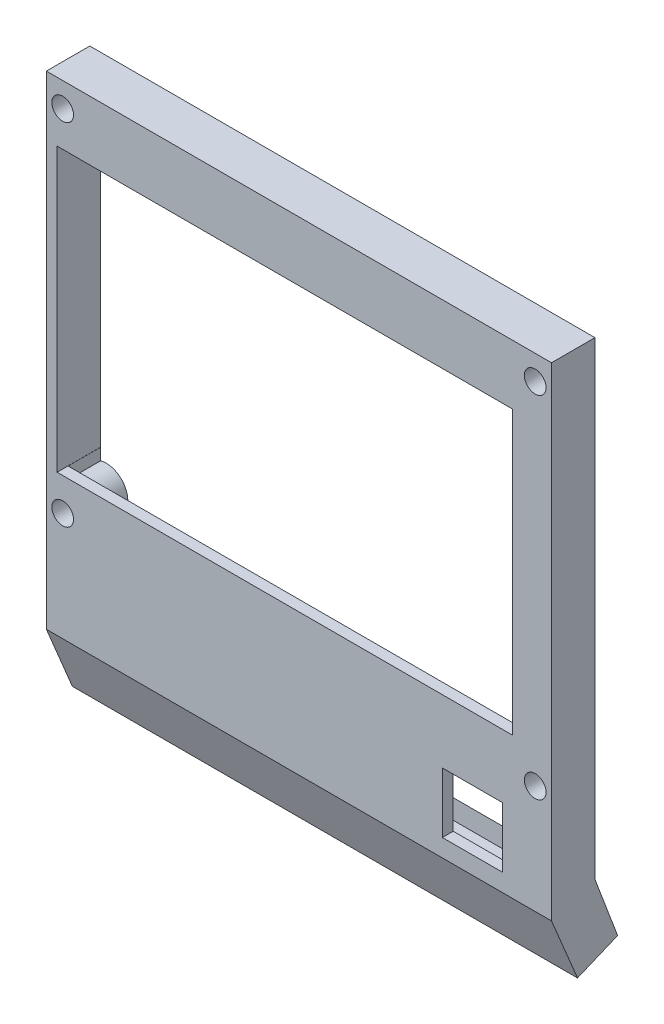
SolidWorks part; units mm, degrees
material "PET"
ref_plane "Front Plane" through (0, 0, 0) normal (0, 0, 1) x (1, 0, 0)
ref_plane "Top Plane" through (0, 0, 0) normal (0, 1, 0) x (1, 0, 0)
ref_plane "Right Plane" through (0, 0, 0) normal (1, 0, 0) x (0, 0, -1)
sketch "Sketch1" plane through (0, 0, 0) normal (0, 0, 1) x (1, 0, 0)
  line L1 (-46.5, -44.5) -> (46.5, -44.5)
  line L2 (-46.5, -44.5) -> (-46.5, 44.5)
  line L3 (-46.5, 44.5) -> (46.5, 44.5)
  line L4 (46.5, -44.5) -> (46.5, 44.5)
  line L5 (-46.5, -44.5) -> (46.5, 44.5) construction
  line L6 (-46.5, 44.5) -> (46.5, -44.5) construction
  point P0 (0, 0)
extrude "Boss-Extrude1" add sketch "Sketch1" along normal blind 8
sketch "Sketch2" plane through (0, 0, 8) normal (0, 0, 1) x (1, 0, 0)
  line L0 (-44.5211, 33.5288) -> (39.3213, 33.5288)
  line L1 (39.3213, 33.5288) -> (39.3213, -18.4712)
  line L2 (39.3213, -18.4712) -> (-44.5211, -18.4712)
  line L3 (-44.5211, -18.4712) -> (-44.5211, 33.5288)
  line L4 (37.5, -30.15) -> (26.4, -30.15)
  line L8 (26.4, -30.15) -> (26.4, -41.25)
  line L12 (37.5, -41.25) -> (26.4, -41.25)
  line L13 (37.5, -41.25) -> (37.5, -30.15)
  circle A0 centre (-43.5, 40) radius 2
  circle A1 centre (43.5, 40) radius 2
  circle A2 centre (-43.5, -24.5) radius 2
  circle A3 centre (43.5, -24.5) radius 2
extrude "Cut-Extrude1" cut sketch "Sketch2" against normal blind 8
shell "Shell6" thickness 2 removed face at (26.4, -35.7, 4) removed face at (31.95, -41.25, 4) removed face at (37.5, -35.7, 4) removed face at (31.95, -30.15, 4) removed face at (-2.5999, -18.4712, 4) removed face at (39.3213, 7.5288, 4) removed face at (-2.5999, 33.5288, 4) removed face at (45.5, 40, 0) removed face at (-44.5211, 7.5288, 4)
sketch "Sketch3" plane through (46.5, 0, 0) normal (1, 0, 0) x (0, 0, -1)
  line L0 (-8, -44.5) -> (-3.2107, -55.993)
  line L9 (0, -44.5) -> (0, -41.8889)
  line L10 (-3.2107, -55.993) -> (4.1738, -52.9158)
  line L11 (-8, -44.5) -> (0, -44.5)
  line L12 (4.1738, -52.9158) -> (0, -41.8889)
extrude "Boss-Extrude2" add sketch "Sketch3" against normal blind 93
sketch "Sketch4" plane through (0, -42.5, 0) normal (0, 1, 0) x (1, 0, 0)
  line L4 (44.5, 0) -> (-44.5, 0)
  line L5 (-44.5, 0) -> (-44.5, -6)
  line L6 (-44.5, -6) -> (44.5, -6)
  line L7 (44.5, -6) -> (44.5, 0)
  line L8 (44.5, 0) -> (-44.5, 0)
  line L9 (-44.5, 0) -> (-44.5, -6)
  line L10 (-44.5, -6) -> (44.5, -6)
  line L11 (44.5, -6) -> (44.5, 0)
  dimension "D1" = 0
extrude "Cut-Extrude2" cut sketch "Sketch4" against normal blind 3
